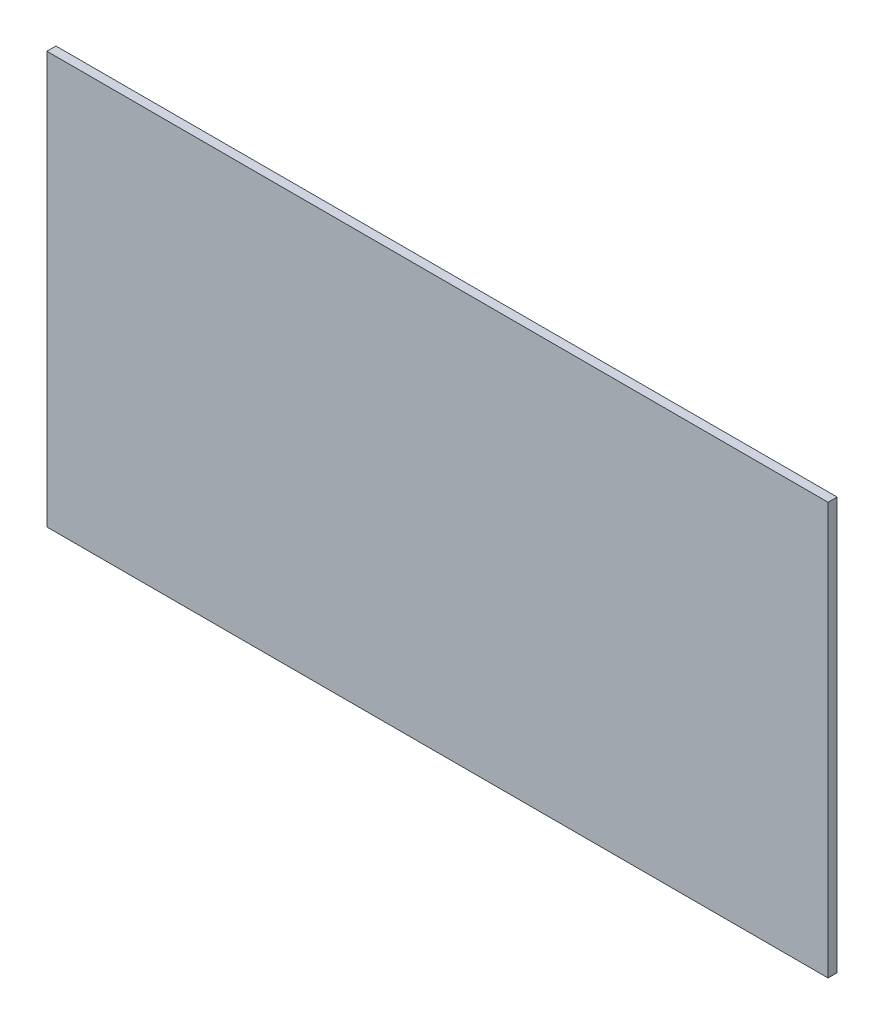
SolidWorks part; units mm, degrees
material "Plain Carbon Steel"
ref_plane "Front Plane" through (0, 0, 0) normal (0, 0, 1) x (1, 0, 0)
ref_plane "Top Plane" through (0, 0, 0) normal (0, 1, 0) x (1, 0, 0)
ref_plane "Right Plane" through (0, 0, 0) normal (1, 0, 0) x (0, 0, -1)
sketch "Sketch1" plane through (0, 0, 0) normal (0, 0, 1) x (1, 0, 0)
  line L1 (0, 0) -> (229.1969, 0)
  line L2 (0, 0) -> (0, 120.8837)
  line L3 (0, 120.8837) -> (229.1969, 120.8837)
  line L4 (229.1969, 0) -> (229.1969, 120.8837)
  dimension "D1" = 229.1969
  dimension "D2" = 120.8837
base flange "Base-Flange1" sketch "Sketch1" thickness 2.6568 reverse thickness direction no parameters "D1"=3.175
sketch "Sketch6" plane through (0, 0, 0) normal (0, 0, 1) x (1, 0, 0)
  line L0 (0, 0) -> (0, 22.3418) construction
  line L1 (0, 120.8837) -> (0, 0) construction
  line L2 (0, 22.3418) -> (0, 98.5418) construction
  line L3 (0, 98.5418) -> (0, 120.8837) construction
  dimension "D1" = 76.2
sketch "Bend-Lines1" [suppressed] plane through (0, 0, 0) normal (0, 1, 0) x (1, 0, 0)
sketch "Bounding-Box1" [suppressed] plane through (0, 0, 0) normal (0, 1, 0) x (1, 0, 0)
sheet metal parameters "Sheet-Metal1" thickness 2.6568 parameters "D1"=3.175
flat pattern "Flat-Pattern1" [suppressed]
sketch "Bend-Lines2" plane through (0, 0, 0) normal (0, 1, 0) x (1, 0, 0)
sketch3d "Bounding-Box2" [suppressed]
  line L0 (0, 0, 0) -> (229.1969, 0, 0) construction
  line L1 (0, 120.8837, 0) -> (229.1969, 120.8837, 0) construction
  line L2 (0, 0, 0) -> (0, 120.8837, 0) construction
  line L3 (229.1969, 0, 0) -> (229.1969, 120.8837, 0) construction
